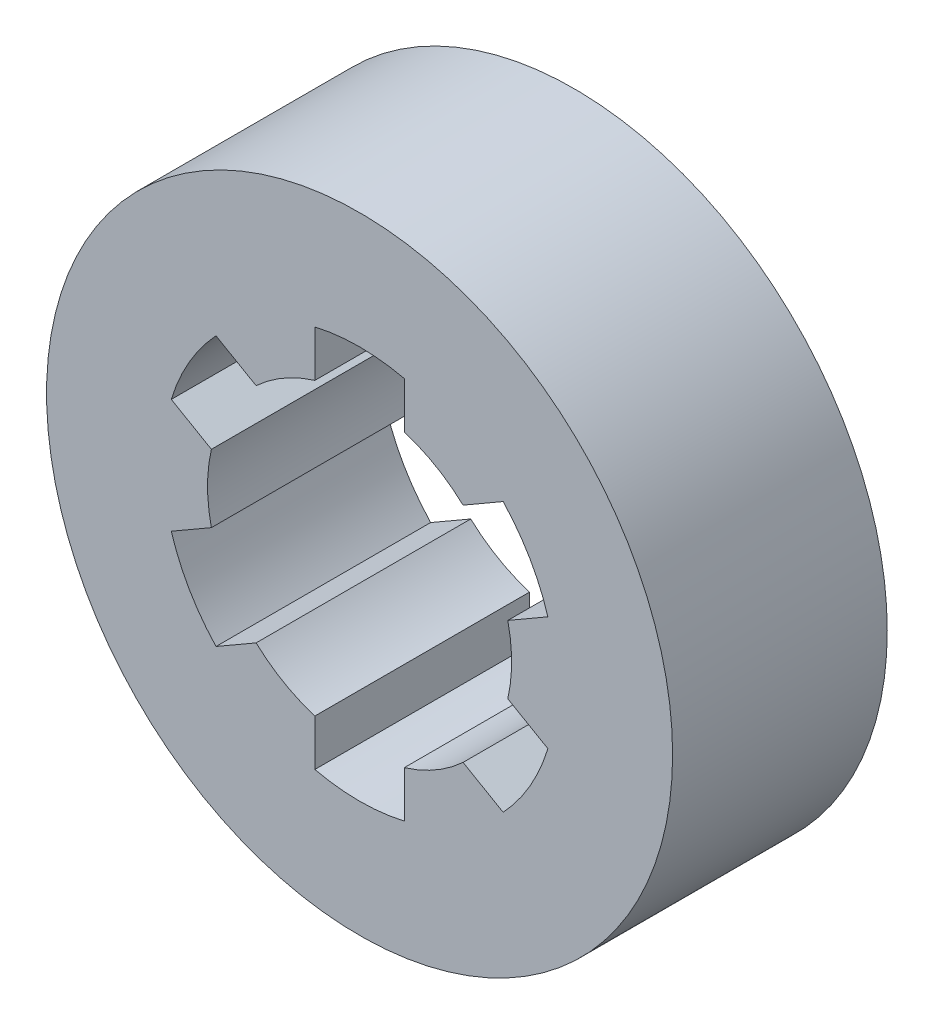
SolidWorks part; units mm, degrees
ref_plane "Front Plane" through (0, 0, 0) normal (0, 0, 1) x (1, 0, 0)
ref_plane "Top Plane" through (0, 0, 0) normal (0, 1, 0) x (1, 0, 0)
ref_plane "Right Plane" through (0, 0, 0) normal (1, 0, 0) x (0, 0, -1)
sketch "Sketch1" plane through (0, 0, 0) normal (0, 0, 1) x (1, 0, 0)
  line L1 (-2.5, 8.124) -> (-2.5, 10.7121)
  line L2 (2.5, 10.7121) -> (2.5, 8.124)
  line L3 (5.7856, 6.2271) -> (8.027, 7.5211)
  line L4 (10.527, 3.191) -> (8.2856, 1.897)
  line L5 (8.2856, -1.897) -> (10.527, -3.191)
  line L6 (8.027, -7.5211) -> (5.7856, -6.2271)
  line L7 (2.5, -8.124) -> (2.5, -10.7121)
  line L8 (-2.5, -10.7121) -> (-2.5, -8.124)
  line L9 (-5.7856, -6.2271) -> (-8.027, -7.5211)
  line L10 (-10.527, -3.191) -> (-8.2856, -1.897)
  line L11 (-8.2856, 1.897) -> (-10.527, 3.191)
  line L12 (-8.027, 7.5211) -> (-5.7856, 6.2271)
  arc A0 (-2.5, 8.124) -> (-5.7856, 6.2271) centre (0, 0) ccw
  circle A1 centre (0, 0) radius 17.5
  arc A2 (-10.527, -3.191) -> (-8.027, -7.5211) centre (0, 0) ccw
  arc A3 (5.7856, 6.2271) -> (2.5, 8.124) centre (0, 0) ccw
  arc A4 (8.2856, -1.897) -> (8.2856, 1.897) centre (0, 0) ccw
  arc A5 (2.5, -8.124) -> (5.7856, -6.2271) centre (0, 0) ccw
  arc A6 (-5.7856, -6.2271) -> (-2.5, -8.124) centre (0, 0) ccw
  arc A7 (-8.2856, 1.897) -> (-8.2856, -1.897) centre (0, 0) ccw
  arc A8 (-8.027, 7.5211) -> (-10.527, 3.191) centre (0, 0) ccw
  arc A9 (2.5, 10.7121) -> (-2.5, 10.7121) centre (0, 0) ccw
  arc A10 (10.527, 3.191) -> (8.027, 7.5211) centre (0, 0) ccw
  arc A11 (8.027, -7.5211) -> (10.527, -3.191) centre (0, 0) ccw
  arc A12 (-2.5, -10.7121) -> (2.5, -10.7121) centre (0, 0) ccw
  point P32 (0, 0)
  dimension "D1" = 35
  dimension "D2" = 17
  dimension "D3" = 22
  dimension "D6" = 6
extrude "Boss-Extrude1" add sketch "Sketch1" along normal blind 12
